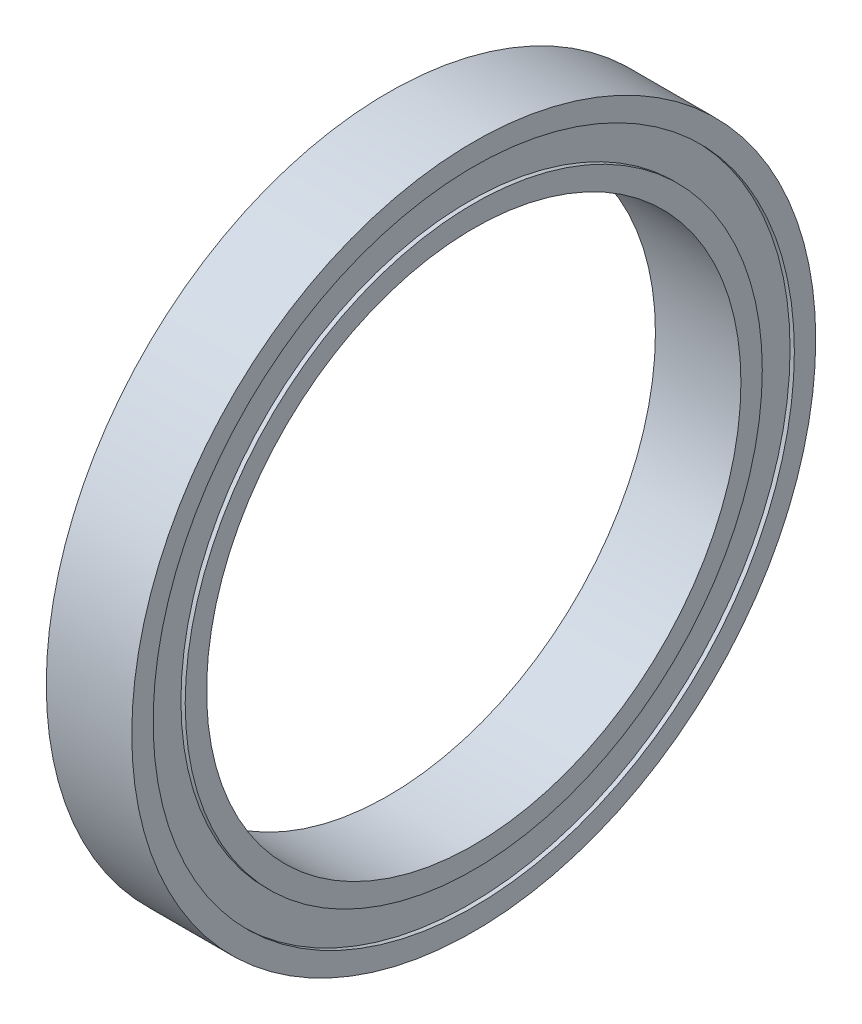
SolidWorks part; units mm, degrees
material "GCr15"
ref_plane "前视基准面" through (0, 0, 0) normal (0, 0, 1) x (1, 0, 0)
ref_plane "上视基准面" through (0, 0, 0) normal (0, 1, 0) x (1, 0, 0)
ref_plane "右视基准面" through (0, 0, 0) normal (1, 0, 0) x (0, 0, -1)
sketch "草图1" plane through (0, 0, 0) normal (1, 0, 0) x (0, 0, -1)
  circle A0 centre (0, 0) radius 12.5
  circle A1 centre (0, 0) radius 16
  dimension "D1" = 32
  dimension "D2" = 25
extrude "凸台-拉伸1" add sketch "草图1" along normal blind 4
sketch "草图2" plane through (4, 0, 0) normal (1, 0, 0) x (0, 0, -1)
  circle A0 centre (0, 0) radius 15
  circle A1 centre (0, 0) radius 13.5
  dimension "D1" = 30
  dimension "D2" = 27
extrude "切除-拉伸1" cut sketch "草图2" against normal blind 0.2
extrude "切除-拉伸2" cut sketch "草图2<2>" along normal blind 0.2 from surface starting at face at (0, 0, -16)
sketch "草图2<2>" plane through (4, 0, 0) normal (1, 0, 0) x (0, 0, -1) same geometry as "草图2"
